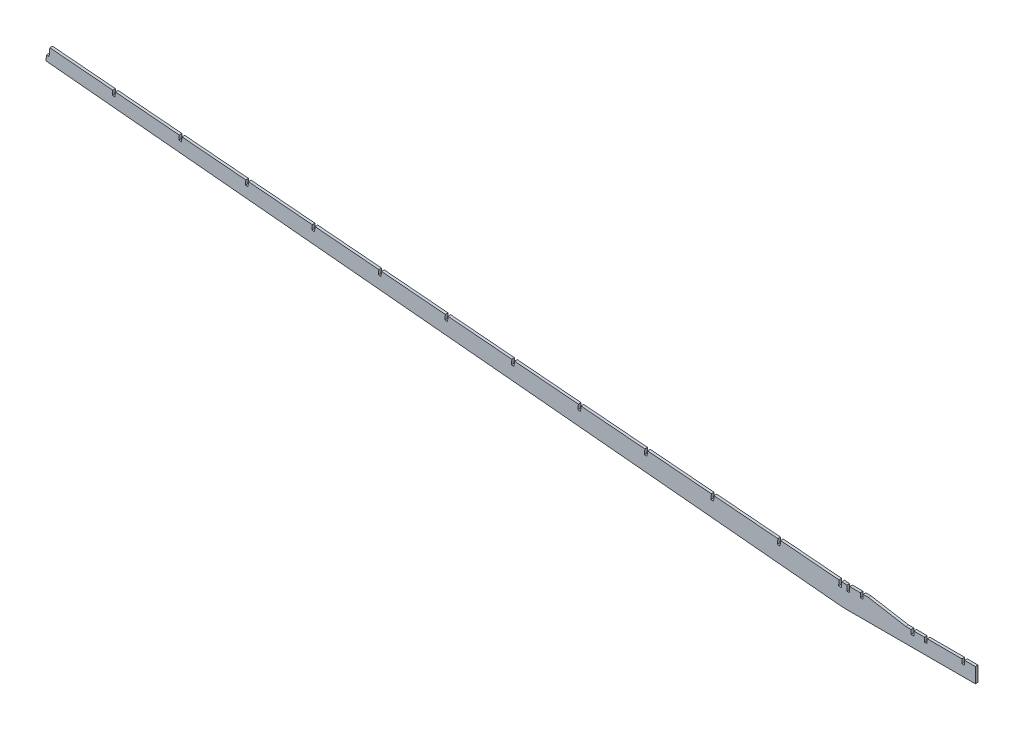
SolidWorks part; units mm, degrees
ref_plane "Front Plane" through (0, 0, 0) normal (0, 0, 1) x (1, 0, 0)
ref_plane "Top Plane" through (0, 0, 0) normal (0, 1, 0) x (1, 0, 0)
ref_plane "Right Plane" through (0, 0, 0) normal (1, 0, 0) x (0, 0, -1)
sketch "Sketch1" plane through (0, 0, 0) normal (0, 0, 1) x (1, 0, 0)
  line L0 (-951.0618, 63.2916) -> (-11.5367, -24.9026)
  line L8 (-8.3728, -25.1683) -> (-6.7788, -6.1851) construction
  line L9 (-6.7788, -6.1851) -> (-9.9426, -5.9194)
  line L10 (-9.9426, -5.9194) -> (-11.5367, -24.9026) construction
  line L11 (-11.5367, -24.9026) -> (-8.3728, -25.1683)
  line L12 (3.175, -25.5459) -> (3.175, -6.4959) construction
  line L13 (3.175, -6.4959) -> (0, -6.4959)
  line L14 (0, -6.4959) -> (0, -25.5459) construction
  line L15 (0, -25.5459) -> (3.175, -25.5459)
  line L17 (-943.9754, 109.7383) -> (-947.3666, 69.3536)
  line L19 (-8.3728, -25.1683) -> (0, -25.5459)
  line L20 (3.175, -25.5459) -> (152.4, -25.5459)
  line L21 (25.4, -0.1459) -> (69.85, -7.7659)
  line L22 (25.4, -0.1459) -> (-2.8123, -0.1459)
  line L23 (-2.8123, -0.1459) -> (-946.5481, 79.1019)
  line L24 (0, -6.4959) -> (0, -0.1459)
  line L25 (3.175, -6.4959) -> (3.175, -0.1459)
  line L26 (-6.7788, -6.1851) -> (-6.2474, 0.1426)
  line L27 (-9.9426, -5.9194) -> (-9.4113, 0.4083)
  line L28 (-9.9426, -5.9194) -> (-946.998, 73.7432)
  line L29 (69.85, -7.7659) -> (152.4, -7.7659)
  line L30 (152.4, -7.7659) -> (152.4, -25.5459)
  line L31 (76.2, -7.7659) -> (76.2, -25.5459)
  line L32 (79.375, -7.7659) -> (79.375, -25.5459)
  line L33 (76.2, -12.8459) -> (79.375, -12.8459)
  line L34 (15.875, -0.1459) -> (15.875, -5.2259)
  line L35 (15.875, -5.2259) -> (19.05, -5.2259)
  line L36 (19.05, -5.2259) -> (19.05, -0.1459)
  line L37 (92.075, -7.7659) -> (92.075, -12.8459)
  line L38 (92.075, -12.8459) -> (95.25, -12.8459)
  line L39 (95.25, -12.8459) -> (95.25, -7.7659)
  line L40 (136.525, -7.7659) -> (136.525, -12.8459)
  line L41 (136.525, -12.8459) -> (139.7, -12.8459)
  line L42 (139.7, -12.8459) -> (139.7, -7.7659)
  line L44 (-951.0618, 63.2916) -> (-950.5305, 69.6193)
  line L45 (-950.5305, 69.6193) -> (-947.3666, 69.3536)
  dimension "D1" = 25.4
  dimension "D2" = 6.35
extrude "Boss-Extrude1" add sketch "Sketch1" along normal blind 3.175 contours L31 L29 L21 L22 L25 L13 L24 L23 L26 L9 L28 L17 L11 L19 L15 L20 | L33 L31 L20 L32 | L29 L32 L20 L30 | L28 L27 L23 L17 | L45 L44 L17 region at (-380.2142, 18.2171, 0) region at (-465.2737, 35.7392, 0) region at (77.7875, -19.1959, 0) region at (115.8875, -16.8176, 0)
sketch "Sketch2" plane through (0, 0, 3.175) normal (0, 0, 1) x (1, 0, 0)
  line L1 (-73.9963, 64.5177) -> (-80.9723, -18.558)
  line L3 (-77.1601, 64.7834) -> (-84.1362, -18.2923)
  line L5 (-153.17, 68.7234) -> (-159.8855, -11.2491)
  line L7 (-232.3428, 72.9404) -> (-238.7996, -3.951)
  line L9 (-311.5203, 77.1018) -> (-317.7101, 3.3887)
  line L11 (-390.6978, 81.2631) -> (-396.6209, 10.7264)
  line L13 (-469.8812, 85.3537) -> (-475.5272, 18.1169)
  line L15 (-549.0652, 89.4374) -> (-554.4332, 25.5108)
  line L17 (-628.256, 93.4393) -> (-633.334, 32.9679)
  line L19 (-707.4489, 97.4177) -> (-712.2332, 40.4425)
  line L21 (-786.6506, 101.2897) -> (-791.1254, 48.0007)
  line L23 (-865.8569, 105.1088) -> (-870.014, 55.603)
  line L25 (-235.5067, 73.2061) -> (-241.9634, -3.6853)
  line L27 (-314.6841, 77.3675) -> (-320.874, 3.6544)
  line L29 (-393.8616, 81.5287) -> (-399.7848, 10.992)
  line L31 (-473.045, 85.6194) -> (-478.6911, 18.3826)
  line L33 (-552.229, 89.7031) -> (-557.5971, 25.7765)
  line L35 (-631.4199, 93.705) -> (-636.4978, 33.2336)
  line L37 (-710.6127, 97.6833) -> (-715.3971, 40.7082)
  line L39 (-789.8145, 101.5554) -> (-794.2893, 48.2664)
  line L41 (-9.9426, -5.9194) -> (-946.998, 73.7432)
  line L43 (-9.4113, 0.4083) -> (-946.5481, 79.1019)
  line L45 (-156.3339, 68.9891) -> (-163.0494, -10.9834)
  line L47 (-869.0207, 105.3745) -> (-873.1778, 55.8686)
extrude "Cut-Extrude1" cut sketch "Sketch2" against normal through all contours L47 L41 L23 | L41 L21 L39 | L41 L19 L37 | L41 L17 L35 | L41 L15 L33 | L41 L13 L31 | L41 L11 L29 | L41 L9 L27 | L41 L7 L25 | L45 L41 L5 | L41 L1 L3 region at (-80.7341, 3.2483, 3.175) region at (-159.7008, 9.9204, 3.175) region at (-238.6674, 16.5925, 3.175) region at (-317.6341, 23.2647, 3.175) region at (-396.6007, 29.9368, 3.175) region at (-475.5673, 36.6089, 3.175) region at (-554.534, 43.281, 3.175) region at (-633.5006, 49.9532, 3.175) region at (-712.4672, 56.6253, 3.175) region at (-791.4339, 63.2974, 3.175) region at (-870.4005, 69.9696, 3.175)
move or copy body "Body-Move/Copy1" [suppressed] bodies to move or copy 102 parameters "D1"=0, "D2"=0, "D3"=0
